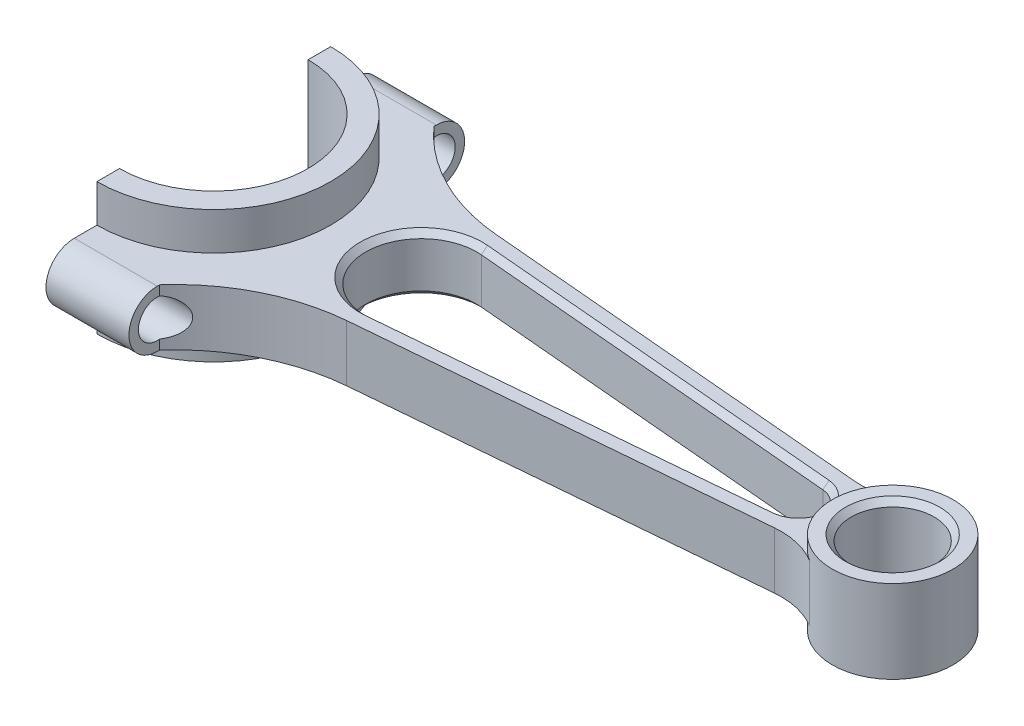
SolidWorks part; units mm, degrees
ref_plane "Front Plane" through (0, 0, 0) normal (0, 0, 1) x (1, 0, 0)
ref_plane "Top Plane" through (0, 0, 0) normal (0, 1, 0) x (1, 0, 0)
ref_plane "Right Plane" through (0, 0, 0) normal (1, 0, 0) x (0, 0, -1)
sketch "Sketch1" plane through (0, 0, 0) normal (0, 1, 0) x (1, 0, 0)
  line L0 (0, 0) -> (0, 50000) construction
  line L1 (0, 0) -> (50000, 0) construction
  line L2 (0, 25) -> (0, 44.5)
  line L3 (0, 44.5) -> (22, 44.5)
  line L4 (22, 44.5) -> (22, 36.3682)
  line L5 (159.2791, 10.6676) -> (55, 19.7909)
  line L6 (0, -25) -> (0, -44.5)
  line L7 (0, -44.5) -> (22, -44.5)
  line L8 (22, -44.5) -> (22, -36.3682)
  line L9 (159.2791, -10.6676) -> (55, -19.7909)
  line L10 (56.2825, 14.6596) -> (155.5229, 5.9772)
  line L11 (155.5229, -5.9772) -> (56.2825, -14.6596)
  arc A0 (0, 25) -> (0, -25) centre (0, 0) cw
  arc A1 (0, 31) -> (0, -31) centre (0, 0) cw
  circle A2 centre (180, 0) radius 16
  circle A3 centre (180, 0) radius 11
  arc A4 (55, 19.7909) -> (22, 36.3682) centre (59.3578, 69.6006) cw
  arc A5 (159.2791, 10.6676) -> (171.5654, 13.5962) centre (161.0222, 30.5915) ccw
  arc A6 (55, -19.7909) -> (22, -36.3682) centre (59.3578, -69.6006) ccw
  arc A7 (159.2791, -10.6676) -> (171.5654, -13.5962) centre (161.0222, -30.5915) cw
  arc A8 (155.5229, 5.9772) -> (155.5229, -5.9772) centre (155, 0) cw
  arc A9 (56.2825, -14.6596) -> (56.2825, 14.6596) centre (55, 0) cw
  dimension "D1" = 32
  dimension "D2" = 22
  dimension "D3" = 31
  dimension "D4" = 25
  dimension "D6" = 50
  dimension "D7" = 20
  dimension "D9" = 5
  dimension "D13" = 5
  dimension "D14" = 6
  dimension "D5" = 22
  dimension "D8" = 89
  dimension "D10" = 5
  dimension "D11" = 100
  dimension "D12" = 125
  dimension "D15" = 180
extrude "Boss-Extrude1" add sketch "Sketch1" along normal mid plane 35 contours A1 L2 A0 L6 region at (0.6932, 0, -28)
extrude "Boss-Extrude2" add sketch "Sketch1<3>" along normal mid plane 22 separate body contours A2 A3 region at (187.5596, 0, -13.5858)
sketch "Sketch1<3>" plane through (0, 0, 0) normal (0, 1, 0) x (1, 0, 0) same geometry as "Sketch1"
extrude "Boss-Extrude3" add sketch "Sketch1<4>" along normal mid plane 15 contours L9 A7 A2 A5 L5 A4 L4 L3 L2 A1 L6 L7 L8 A6 L11 A9 L10 A8 region at (1.9328, 0, -37.75)
sketch "Sketch1<4>" plane through (0, 0, 0) normal (0, 1, 0) x (1, 0, 0) same geometry as "Sketch1"
hole_wizard "Ø10.0mm Dowel Hole1" positions "Sketch2" profile "Sketch3" hole size "Ø10.0" standard "ANSI Metric" end condition through all
sketch "Sketch2" plane through (0, 0, 0) normal (-1, 0, 0) x (0, 0, 1)
  line L0 (44.5, 7.5) -> (44.5, -7.5) construction
  point P0 (-37, 0)
  point P2 (37, 0)
  point P4 (0, 0)
  dimension "D1" = 74
  dimension "D2" = 7.5
sketch "Sketch3" plane through (0, 0, -37) normal (0, 1, 0) x (0, 0, 1)
  line L0 (0, 0) -> (0, 196)
  line L1 (0, 196) -> (5, 196)
  line L2 (5, 196) -> (5, 0)
  line L5 (5, 0) -> (0, 0)
  line L11 (0, -6.35) -> (0, 107.95) construction
  dimension "Thru Hole Dia." = 10
  dimension "Thru Hole Depth" = 196
fillet "Fillet1" 2 edges at (11, 7.5, 44.5) (11, -7.5, 44.5) type full round first side face at (62.8875, 7.5, 0) second side face at (62.8875, -7.5, 0) middle face at (11, 0, 44.5)
fillet "Fillet2" 2 edges at (11, 7.5, -44.5) (11, -7.5, -44.5) type full round first side face at (62.8875, 7.5, -1.0714) second side face at (62.8875, -7.5, -1.0714) middle face at (11, 0, -44.5)
chamfer "Chamfer1" distance 1.5 angle 45 8 edges at (105.9027, -7.5, 10.3184) (40.2844, -7.5, 0) (161, -7.5, 0) (105.9027, -7.5, -10.3184) (105.9027, 7.5, -10.3184) (161, 7.5, 0) (40.2844, 7.5, 0) (105.9027, 7.5, 10.3184)
chamfer "Chamfer2" distance 1.5 angle 45 2 edges at (180, -11, 11) (180, 11, 11)
